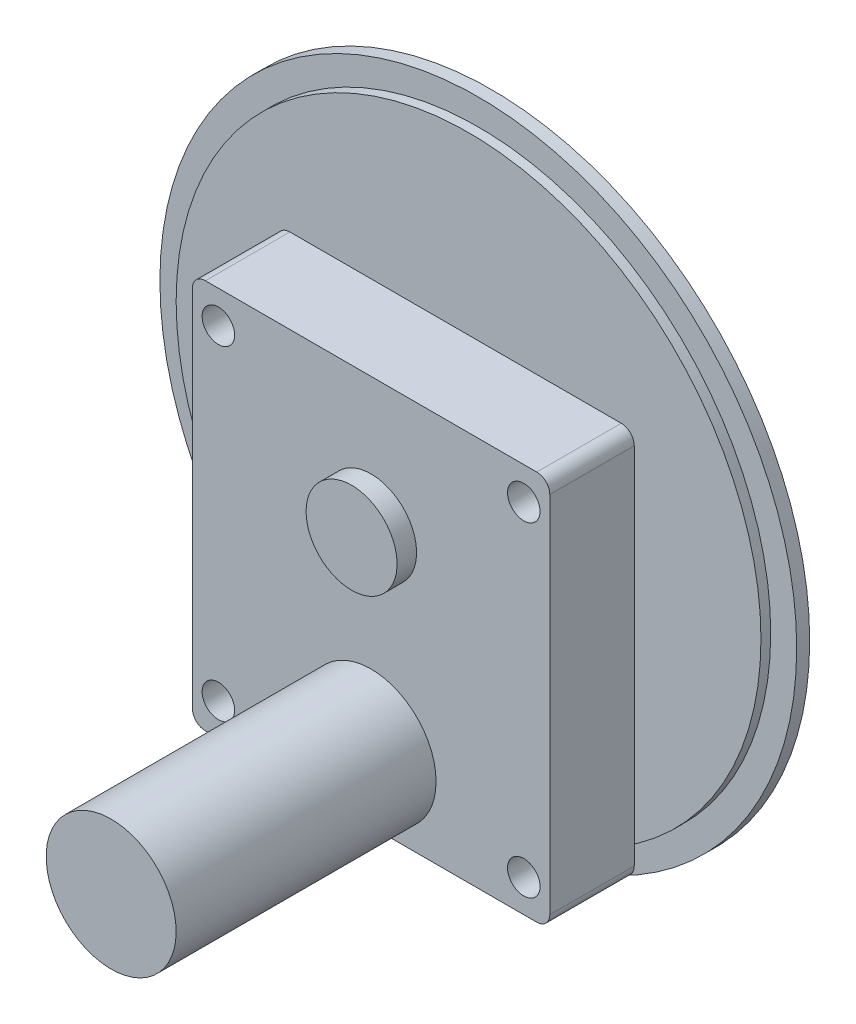
SolidWorks part; units mm, degrees
ref_plane "Front Plane" through (0, 0, 0) normal (0, 0, 1) x (1, 0, 0)
ref_plane "Top Plane" through (0, 0, 0) normal (0, 1, 0) x (1, 0, 0)
ref_plane "Right Plane" through (0, 0, 0) normal (1, 0, 0) x (0, 0, -1)
sketch "Sketch1" plane through (0, 0, 0) normal (0, 0, 1) x (1, 0, 0)
  line L1 (-34.925, -50.8) -> (34.925, -50.8)
  line L2 (-34.925, -50.8) -> (-34.925, 25.4)
  line L3 (-34.925, 25.4) -> (34.925, 25.4)
  line L4 (34.925, -50.8) -> (34.925, 25.4)
  circle A0 centre (0, 0) radius 57.15
  circle A1 centre (0, 0) radius 62.23
  circle A2 centre (-29.845, 19.05) radius 3.175
  circle A3 centre (29.845, 19.05) radius 3.175
  circle A4 centre (-29.845, -44.45) radius 3.175
  circle A5 centre (29.845, -44.45) radius 3.175
  circle A6 centre (0, -36.83) radius 12.7
  circle A7 centre (0, 0) radius 8.89
  circle A8 centre (0, -36.83) radius 7.62
  dimension "D1" = 114.3
  dimension "D4" = 124.46
  dimension "D6" = 17.78
  dimension "D7" = 6.35
  dimension "D8" = 6.35
  dimension "D9" = 6.35
  dimension "D10" = 6.35
  dimension "D22" = 25.4
  dimension "D23" = 15.24
  dimension "D24" = 50.8
  dimension "D2" = 76.2
  dimension "D3" = 69.85
  dimension "D5" = 13.97
  dimension "D11" = 6.35
  dimension "D12" = 5.08
  dimension "D13" = 6.35
  dimension "D14" = 5.08
  dimension "D15" = 5.08
  dimension "D16" = 6.35
  dimension "D17" = 6.35
  dimension "D18" = 5.08
  dimension "D19" = 0
  dimension "D20" = 34.925
  dimension "D21" = 34.925
extrude "Boss-Extrude1" add sketch "Sketch1" against normal blind 6.35 contours L4 A0 L2 L3 | L1 L4 L3 L2 A7 A6 A5 A4 A3 A2 | L1 A0 | A6 A8 | A8 | A7 | A3 | A5 | A4 | A2 region at (0, -10.2608, 0) region at (0, -53.3525, 0) region at (-24.5241, 49.9164, 0) region at (-29.845, 19.05, 0) region at (29.845, 19.05, 0) region at (-29.845, -44.45, 0) region at (29.845, -44.45, 0) region at (-12.3408, -36.83, 0) region at (0, 0, 0) region at (0, -36.83, 0)
extrude "Boss-Extrude2" add sketch "Sketch1<5>" against normal blind 4.445 contours A1 A0 | A0 L2 L1 | A0 L1 L4 region at (-32.1114, -49.0064, 0) region at (32.1114, -49.0064, 0) region at (-60.4699, 0, 0)
sketch "Sketch1<5>" plane through (0, 0, 0) normal (0, 0, 1) x (1, 0, 0) same geometry as "Sketch1"
extrude "Cut-Extrude1" cut sketch "Sketch1<6>" against normal blind 1.905 contours A1 A0 | A0 L2 L1 | A0 L1 L4 region at (-32.1114, -49.0064, 0) region at (32.1114, -49.0064, 0) region at (-60.4699, 0, 0)
sketch "Sketch1<6>" plane through (0, 0, 0) normal (0, 0, 1) x (1, 0, 0) same geometry as "Sketch1"
extrude "Boss-Extrude5" add sketch "Sketch1<12>" along normal blind 69.85 contours A6 A8 | A8 region at (-12.3408, -36.83, 0) region at (0, -36.83, 0)
sketch "Sketch1<12>" plane through (0, 0, 0) normal (0, 0, 1) x (1, 0, 0) same geometry as "Sketch1"
extrude "Cut-Extrude3" cut sketch "Sketch1<13>" along normal blind 3.81 contours A6
sketch "Sketch1<13>" plane through (0, 0, 0) normal (0, 0, 1) x (1, 0, 0) same geometry as "Sketch1"
extrude "Boss-Extrude8" add sketch "Sketch1<17>" along normal blind 19.05 contours L2 A0 L1 L4 L3 A7 A6 A5 A4 A3 A2 | A0 L2 L1 | A0 L1 L4 region at (-32.1114, -49.0064, 0) region at (0, -10.2608, 0) region at (32.1114, -49.0064, 0)
sketch "Sketch1<17>" plane through (0, 0, 0) normal (0, 0, 1) x (1, 0, 0) same geometry as "Sketch1"
extrude "Boss-Extrude9" add sketch "Sketch1<18>" along normal blind 22.86 contours A7 region at (0, 0, 0)
sketch "Sketch1<18>" plane through (0, 0, 0) normal (0, 0, 1) x (1, 0, 0) same geometry as "Sketch1"
extrude "Cut-Extrude6" cut sketch "Sketch1<22>" along normal blind 2.54 contours L2 A0 L1 L4 L3 A7 A6 A5 A4 A3 A2 | A0 L1 L4 | A0 L2 L1 region at (-32.1114, -49.0064, 0) region at (0, -10.2608, 0) region at (32.1114, -49.0064, 0)
sketch "Sketch1<22>" plane through (0, 0, 0) normal (0, 0, 1) x (1, 0, 0) same geometry as "Sketch1"
fillet "Fillet1" radius 2.54 4 edges at (-34.925, -50.8, 10.795) (34.925, -50.8, 10.795) (34.925, 25.4, 10.795) (-34.925, 25.4, 10.795)
